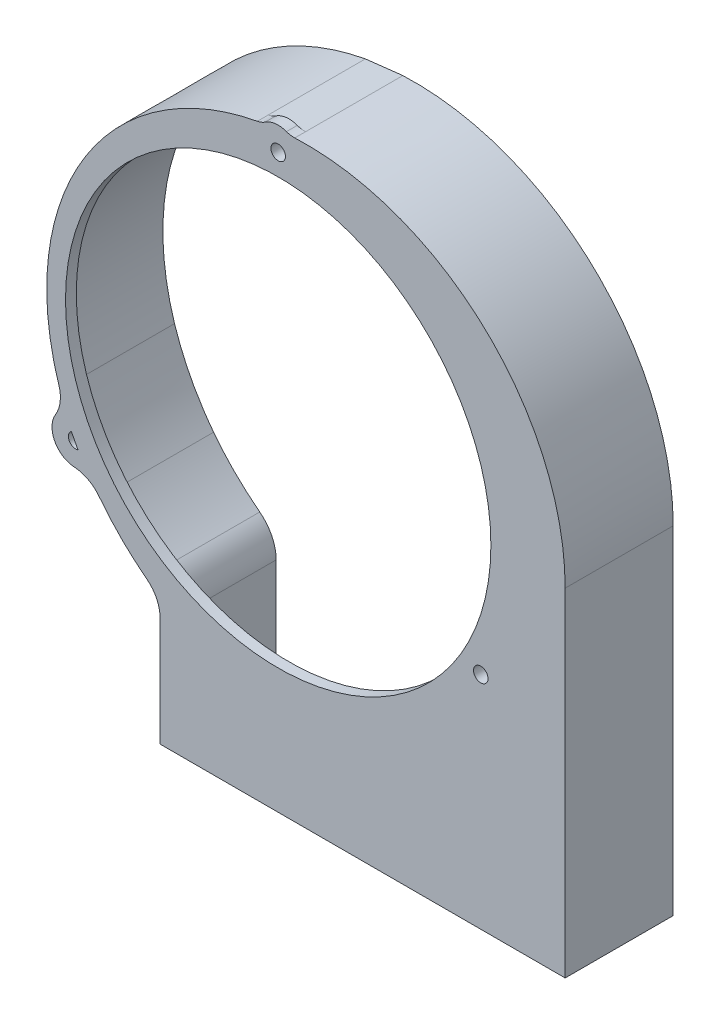
SolidWorks part; units mm, degrees
ref_plane "Front Plane" through (0, 0, 0) normal (0, 0, 1) x (1, 0, 0)
ref_plane "Top Plane" through (0, 0, 0) normal (0, 1, 0) x (1, 0, 0)
ref_plane "Right Plane" through (0, 0, 0) normal (1, 0, 0) x (0, 0, -1)
sketch "Sketch1" plane through (0, 0, 0) normal (0, 0, 1) x (1, 0, 0)
  line L0 (-2.9, 34.641) -> (2.9, 34.641) construction
  line L1 (0, 37.541) -> (0, -32.5) construction
  line L2 (-2.9, 34.641) -> (-2.9, 33.7141) construction
  line L3 (2.9, 34.641) -> (2.9, 33.7141) construction
  line L4 (28.55, -19.832) -> (27.7473, -19.3685) construction
  line L5 (31.45, -14.809) -> (30.6473, -14.3456) construction
  line L6 (-31.45, -14.809) -> (-30.6473, -14.3456) construction
  line L7 (-28.55, -19.832) -> (-27.7473, -19.3685) construction
  line L8 (0, 0) -> (2.9, 32.3704) construction
  line L9 (0, 0) -> (26.5366, -18.6636) construction
  line L10 (0, 0) -> (-29.4836, -13.6737) construction
  line L11 (0, 0) -> (-4.9858, 10.9152) construction
  line L12 (22.4164, -0.1297) -> (13.1694, 0.7526) construction
  line L13 (-11.0959, 19.478) -> (-7.2365, 11.0288) construction
  line L14 (12.7895, -3.2293) -> (22.0364, -4.1116) construction
  line L15 (-3.5981, 12.6907) -> (-7.4575, 21.1399) construction
  line L16 (-117.663, 0) -> (152.468, 0) construction
  line L17 (-11.3205, -19.3483) -> (-5.933, -11.7813) construction
  line L18 (-9.1914, -9.4614) -> (-14.579, -17.0283) construction
  line L19 (0, 0) -> (-6.9599, -9.7754) construction
  line L20 (-17.5, -50) -> (42.5, -50)
  line L21 (0, 0) -> (23.991, -2.289) construction
  line L22 (-17.5, -50) -> (-17.5, -33.7719)
  line L23 (0, -32.5) -> (-11.3205, -32.5) construction
  line L24 (42.5, -50) -> (42.5, -32.5)
  line L27 (10, -109.7237) -> (10, 118.4601) construction
  line L28 (42.5, -32.5) -> (42.5, 0) construction
  line L30 (42.5, -32.5) -> (42.5, 0)
  line L31 (-31.75, -14.2894) -> (-31.4852, -14.1365)
  line L32 (-28.25, -20.3516) -> (-28.2308, -20.3405)
  line L34 (-31.75, -14.2894) -> (-30.9473, -13.826) construction
  line L35 (-28.25, -20.3516) -> (-27.4473, -19.8881) construction
  arc A0 (-4.2059, 32.2267) -> (-30.0121, -12.471) centre (0, 0) ccw construction
  circle A1 centre (0, 34.641) radius 1.075 construction
  arc A2 (2.9, 34.641) -> (-2.9, 34.641) centre (0, 34.641) ccw construction
  arc A3 (28.55, -19.832) -> (31.45, -14.809) centre (30, -17.3205) ccw construction
  circle A4 centre (30, -17.3205) radius 1.075 construction
  arc A5 (-31.45, -14.809) -> (-28.55, -19.832) centre (-30, -17.3205) ccw construction
  circle A6 centre (-30, -17.3205) radius 1.075 construction
  arc A7 (-25.8062, -19.7558) -> (25.8062, -19.7558) centre (0, 0) ccw construction
  arc A8 (30.0121, -12.471) -> (4.2059, 32.2267) centre (0, 0) ccw construction
  arc A9 (-27.7473, -19.3685) -> (-25.8062, -19.7558) centre (-26.9973, -20.6676) cw construction
  arc A10 (-30.6473, -14.3456) -> (-30.0121, -12.471) centre (-31.3973, -13.0465) ccw construction
  arc A11 (27.7473, -19.3685) -> (25.8062, -19.7558) centre (26.9973, -20.6676) ccw construction
  arc A12 (30.6473, -14.3456) -> (30.0121, -12.471) centre (31.3973, -13.0465) cw construction
  arc A13 (2.9, 33.7141) -> (4.2059, 32.2267) centre (4.4, 33.7141) ccw construction
  arc A14 (-2.9, 33.7141) -> (-4.2059, 32.2267) centre (-4.4, 33.7141) cw construction
  arc A15 (-13.2873, 20.1062) -> (-16.8496, -17.2308) centre (0, 0) ccw construction
  arc A16 (11.8328, 1.9963) -> (-1.9855, 11.8346) centre (0, 0) ccw construction
  arc A17 (24.0561, 1.454) -> (-6.4975, 23.2076) centre (0, 0) ccw construction
  arc A18 (-10.7688, -21.5602) -> (23.3471, -5.9768) centre (0, 0) ccw construction
  arc A19 (-4.1876, -11.2456) -> (11.2418, -4.1978) centre (0, 0) ccw construction
  arc A20 (-7.6452, 9.2494) -> (-9.2563, -7.6368) centre (0, 0) ccw construction
  arc A21 (-11.3205, -19.3483) -> (-10.7688, -21.5602) centre (-10.0986, -20.2183) ccw construction
  arc A22 (-14.579, -17.0283) -> (-16.8496, -17.2308) centre (-15.8009, -16.1583) cw construction
  arc A23 (-9.1914, -9.4614) -> (-9.2563, -7.6368) centre (-10.4134, -8.5914) ccw construction
  arc A24 (-5.933, -11.7813) -> (-4.1876, -11.2456) centre (-4.711, -12.6513) cw construction
  arc A25 (12.7895, -3.2293) -> (11.2418, -4.1978) centre (12.647, -4.7226) ccw construction
  arc A26 (22.0364, -4.1116) -> (23.3471, -5.9768) centre (21.894, -5.6048) cw construction
  arc A27 (13.1694, 0.7526) -> (11.8328, 1.9963) centre (13.3119, 2.2458) cw construction
  arc A28 (-11.0959, 19.478) -> (-13.2873, 20.1062) centre (-12.4603, 18.8548) ccw construction
  arc A29 (-6.4975, 23.2076) -> (-7.4575, 21.1399) centre (-6.0931, 21.7631) ccw construction
  arc A30 (-3.5981, 12.6907) -> (-1.9855, 11.8346) centre (-2.2337, 13.3139) ccw construction
  arc A31 (-7.2365, 11.0288) -> (-7.6452, 9.2494) centre (-8.6009, 10.4055) cw construction
  arc A32 (24.0561, 1.454) -> (22.4164, -0.1297) centre (22.5588, 1.3635) cw construction
  circle A33 centre (0, 0) radius 31 construction
  arc A34 (-32.9882, -15.4983) -> (-30.1991, -20.8148) centre (-30, -17.3205) ccw
  arc A35 (1.2258, 37.9193) -> (-1.9352, 37.5573) centre (0, 34.641) ccw
  circle A36 centre (0, 0) radius 31.5
  arc A37 (3.5, 34.641) -> (-3.5, 34.641) centre (0, 34.641) ccw construction
  circle A38 centre (0, 34.641) radius 1.075
  circle A39 centre (30, -17.3205) radius 1.075
  circle A40 centre (-30, -17.3205) radius 1.075
  arc A41 (-17.5, -33.7719) -> (-19.4614, -29.8011) centre (-22.5, -33.7719) ccw
  arc A42 (-31.75, -14.2894) -> (-28.25, -20.3516) centre (-30, -17.3205) ccw construction
  arc A43 (-26.5184, -22.7609) -> (-30.1991, -20.8148) centre (-30.4836, -25.8067) ccw
  arc A44 (-32.4964, -11.3671) -> (-32.9882, -15.4983) centre (-37.2571, -12.8951) cw
  arc A45 (-1.9352, 37.5573) -> (-3.0921, 37.0875) centre (-3.6722, 40.1749) cw
  arc A46 (2.459, 37.7232) -> (1.2258, 37.9193) centre (2.326, 40.8618) cw
  ellipse E0 centre (4.1114, 0) end of major axis (-34.2773, 0) minor radius 37.7582 (42.5, 0) -> (2.459, 37.7232) ccw
  ellipse E1 centre (4.1114, 0) end of major axis (-34.2773, 0) minor radius 37.7582 (-26.5184, -22.7609) -> (-19.4614, -29.8011) ccw
  ellipse E2 centre (4.1114, 0) end of major axis (-34.2773, 0) minor radius 37.7582 (-3.0921, 37.0875) -> (-32.4964, -11.3671) ccw
  point P2 (10, -41.25)
  point P25 (32.5, 0)
  point P60 (0, 0)
  point P88 (10, 0)
  dimension "D1" = 65
  dimension "D2" = 2.15
  dimension "D3" = 5.8
  dimension "D6" = 1.5
  dimension "D7" = 8.4
  dimension "D8" = 24
  dimension "D12" = 1.5
  dimension "D13" = 1.5
  dimension "D14" = 62
  dimension "D17" = 5
  dimension "D23" = 5
  dimension "D24" = 3.1414
  dimension "D5" = 120
  dimension "D9" = 2
  dimension "D10" = 2
  dimension "D15" = 60
  dimension "D16" = 50
  dimension "D18" = 10
  dimension "D22" = 60
  dimension "D19" = 0.6
  dimension "D20" = 0.6
  dimension "D21" = 0.5
  dimension "D4" = 3
  dimension "D11" = 3
extrude "extrude-base" add sketch "Sketch1" along normal blind 1.6 contours A45 E2 A44 A34 A43 E1 A41 L22 L20 L24 L30 E0 A46 A35 A36 A38 A39 A40 region at (-16.3311, -41.8859, 0)
sketch "Sketch10" plane through (0, 0, 1.6) normal (0, 0, 1) x (1, 0, 0)
  line L6 (-17.5, -33.7719) -> (-17.5, -50)
  line L7 (-17.5, -50) -> (42.5, -50)
  line L8 (42.5, -50) -> (42.5, 0)
  line L9 (-17.5, -33.7719) -> (-17.5, -50)
  line L10 (-17.5, -50) -> (-16.3, -50)
  line L11 (42.5, -50) -> (42.5, 0)
  line L12 (-16.3, -48.8) -> (-16.3, -50)
  line L13 (41.3, -48.8) -> (41.3, -50)
  line L14 (41.3, -50) -> (42.5, -50)
  line L15 (-16.3, -33.7719) -> (-16.3, -48.8)
  line L16 (-16.3, -48.8) -> (41.3, -48.8)
  line L17 (41.3, -48.8) -> (41.3, 0)
  line L18 (-16.3, -33.7719) -> (-16.3, -48.8)
  line L19 (-2.8704, 35.9081) -> (2.5098, 36.5243)
  line L20 (41.3, -48.8) -> (41.3, 0)
  line L21 (-3.0921, 37.0875) -> (2.459, 37.7232)
  arc A14 (-3.0921, 37.0875) -> (-1.9352, 37.5573) centre (-3.6722, 40.1749) ccw
  arc A15 (-32.9882, -15.4983) -> (-32.4964, -11.3671) centre (-37.2571, -12.8951) ccw
  arc A16 (-32.9882, -15.4983) -> (-30.1991, -20.8148) centre (-30, -17.3205) ccw
  arc A17 (-26.5184, -22.7609) -> (-30.1991, -20.8148) centre (-30.4836, -25.8067) ccw
  arc A18 (-17.5, -33.7719) -> (-19.4614, -29.8011) centre (-22.5, -33.7719) ccw
  arc A19 (1.2258, 37.9193) -> (2.459, 37.7232) centre (2.326, 40.8618) ccw
  arc A20 (1.2258, 37.9193) -> (-1.9352, 37.5573) centre (0, 34.641) ccw
  arc A22 (-32.379, -11.798) -> (-32.4964, -11.3671) centre (-37.2571, -12.8951) ccw
  arc A24 (-26.5184, -22.7609) -> (-26.826, -22.3976) centre (-30.4836, -25.8067) ccw
  arc A25 (-17.5, -33.7719) -> (-19.4614, -29.8011) centre (-22.5, -33.7719) ccw
  arc A35 (-2.8704, 35.9081) -> (-1.2717, 36.5575) centre (-3.6722, 40.1749) ccw
  arc A36 (-31.9637, -16.1231) -> (-31.3538, -11.0004) centre (-37.2571, -12.8951) ccw
  arc A37 (-31.9637, -16.1231) -> (-30.1309, -19.6168) centre (-30, -17.3205) ccw
  arc A38 (-25.5667, -22.03) -> (-30.1309, -19.6168) centre (-30.4836, -25.8067) ccw
  arc A39 (-16.3, -33.7719) -> (-18.7322, -28.8481) centre (-22.5, -33.7719) ccw
  arc A40 (0.8055, 36.7953) -> (2.5098, 36.5243) centre (2.326, 40.8618) ccw
  arc A41 (0.8055, 36.7953) -> (-1.2717, 36.5575) centre (0, 34.641) ccw
  arc A46 (-16.3, -33.7719) -> (-18.7322, -28.8481) centre (-22.5, -33.7719) ccw
  ellipse E6 centre (4.1114, 0) end of major axis (-34.2773, 0) minor radius 37.7582 (-3.0921, 37.0875) -> (-32.4964, -11.3671) ccw
  ellipse E7 centre (4.1114, 0) end of major axis (-34.2773, 0) minor radius 37.7582 (-26.5184, -22.7609) -> (-19.4614, -29.8011) ccw
  ellipse E8 centre (4.1114, 0) end of major axis (-34.2773, 0) minor radius 37.7582 (42.5, 0) -> (2.459, 37.7232) ccw
  ellipse E9 centre (4.1114, 0) end of major axis (-34.2773, 0) minor radius 37.7582 (-3.0921, 37.0875) -> (-32.4964, -11.3671) ccw
  ellipse E10 centre (4.1114, 0) end of major axis (-34.2773, 0) minor radius 37.7582 (-26.5184, -22.7609) -> (-19.4614, -29.8011) ccw
  ellipse E11 centre (4.1114, 0) end of major axis (-34.2773, 0) minor radius 37.7582 (42.5, 0) -> (2.459, 37.7232) ccw
  spline S0 degree 3 poles (2530.5832, -5387.9475) (692.9967, -896.5243) (145.8987, 98.1948) (-11.4801, 33.2143) (-12.6478, 32.6607) (-14.3638, 31.7341) (-14.9312, 31.4083) (-16.0415, 30.7315) (-16.5857, 30.3799) (-19.2528, 28.5568) (-21.2158, 26.8924) (-23.8996, 24.0813) (-24.7539, 23.086) (-26.3349, 21.032) (-27.7971, 18.9073) (-29.0256, 16.6438) (-29.8578, 14.8931) (-30.1203, 14.3007) (-30.6148, 13.0978) (-30.8473, 12.486) (-31.9191, 9.4172) (-32.5015, 6.9082) (-32.8915, 3.7057) (-32.9525, 3.0618) (-33.0396, 1.7673) (-33.0659, 1.115) (-33.0911, -0.8408) (-33.037, -2.1344) (-17.0784, -169.1919) (1132.0811, -170.6193) (5943.9195, 359.0893) knots -8.074292 -8.074292 -8.074292 -8.074292 0.125 0.125 0.1875 0.1875 0.21875 0.21875 0.25 0.25 0.375 0.375 0.4375 0.4375 0.5 0.5625 0.5625 0.59375 0.59375 0.625 0.625 0.75 0.75 0.78125 0.78125 0.8125 0.8125 0.875 0.875 8.946378 8.946378 8.946378 8.946378 only from (-2.8704, 35.9081) to (-31.3538, -11.0004)
  spline S1 degree 3 poles (3866.3832, 4527.9049) (440.261, 875.0538) (-131.6317, 83.3001) (98.4859, -146.1976) (1052.9272, 568.8562) (4552.9565, 3835.6232) knots -47.451296 -47.451296 -47.451296 -47.451296 0.5 0.5 53.54289 53.54289 53.54289 53.54289 only from (-25.5667, -22.03) to (-18.7322, -28.8481)
  spline S2 degree 3 poles (-5764.2897, -1464.7865) (-908.0196, -474.8461) (72.9243, -147.1511) (40.2816, 8.5858) (39.966, 9.7833) (39.3964, 11.5631) (39.19, 12.1551) (38.749, 13.3213) (38.5142, 13.8965) (37.2709, 16.7338) (36.055, 18.8812) (33.9007, 21.9191) (33.1227, 22.9055) (31.4857, 24.7761) (30.6249, 25.6643) (28.8208, 27.3489) (27.8776, 28.1452) (26.4006, 29.2706) (25.8979, 29.6341) (24.8714, 30.3378) (24.3462, 30.6789) (21.6878, 32.3115) (19.4634, 33.3865) (15.986, 34.6657) (14.8032, 35.0362) (12.9926, 35.5057) (12.3825, 35.6478) (11.1621, 35.9003) (10.5505, 36.0112) (-168.8774, 63.9896) (-470.9936, -1191.6349) (-1099.6628, -5846.5117) knots -7.869177 -7.869177 -7.869177 -7.869177 0.125 0.125 0.1875 0.1875 0.21875 0.21875 0.25 0.25 0.375 0.375 0.4375 0.4375 0.5 0.5 0.5625 0.5625 0.59375 0.59375 0.625 0.625 0.75 0.75 0.8125 0.8125 0.84375 0.84375 0.875 0.875 9.988994 9.988994 9.988994 9.988994 only from (41.3, 0) to (2.5098, 36.5243)
  spline S3 degree 3 poles (-2.8704, 35.9081) (-5.4365, 35.426) (-7.9084, 34.689) (-11.4801, 33.2143) (-12.6478, 32.6607) (-14.3638, 31.7341) (-14.9312, 31.4083) (-16.0415, 30.7315) (-16.5857, 30.3799) (-19.2528, 28.5568) (-21.2158, 26.8924) (-23.8996, 24.0813) (-24.7539, 23.086) (-26.3349, 21.032) (-27.7971, 18.9073) (-29.0256, 16.6438) (-29.8578, 14.8931) (-30.1203, 14.3007) (-30.6148, 13.0978) (-30.8473, 12.486) (-31.9191, 9.4172) (-32.5015, 6.9082) (-32.8915, 3.7057) (-32.9525, 3.0618) (-33.0396, 1.7673) (-33.0659, 1.115) (-33.0911, -0.8408) (-33.037, -2.1344) (-32.6691, -5.9853) (-32.1521, -8.5132) (-31.3538, -11.0004) knots 0 0 0 0 0.125 0.125 0.1875 0.1875 0.21875 0.21875 0.25 0.25 0.375 0.375 0.4375 0.4375 0.5 0.5625 0.5625 0.59375 0.59375 0.625 0.625 0.75 0.75 0.78125 0.78125 0.8125 0.8125 0.875 0.875 1 1 1 1
  spline S4 degree 3 poles (-25.5667, -22.03) (-24.5781, -23.3171) (-23.5128, -24.5275) (-21.2343, -26.7999) (-20.021, -27.8619) (-18.7322, -28.8481) knots 0 0 0 0 0.5 0.5 1 1 1 1
  spline S5 degree 3 poles (41.3, 0) (41.3, 2.5028) (41.0413, 4.9614) (40.2816, 8.5858) (39.966, 9.7833) (39.3964, 11.5631) (39.19, 12.1551) (38.749, 13.3213) (38.5142, 13.8965) (37.2709, 16.7338) (36.055, 18.8812) (33.9007, 21.9191) (33.1227, 22.9055) (31.4857, 24.7761) (30.6249, 25.6643) (28.8208, 27.3489) (27.8776, 28.1452) (26.4006, 29.2706) (25.8979, 29.6341) (24.8714, 30.3378) (24.3462, 30.6789) (21.6878, 32.3115) (19.4634, 33.3865) (15.986, 34.6657) (14.8032, 35.0362) (12.9926, 35.5057) (12.3825, 35.6478) (11.1621, 35.9003) (10.5505, 36.0112) (7.4849, 36.4892) (5.0092, 36.6302) (2.5098, 36.5243) knots 0 0 0 0 0.125 0.125 0.1875 0.1875 0.21875 0.21875 0.25 0.25 0.375 0.375 0.4375 0.4375 0.5 0.5 0.5625 0.5625 0.59375 0.59375 0.625 0.625 0.75 0.75 0.8125 0.8125 0.84375 0.84375 0.875 0.875 1 1 1 1
  spline S6 degree 2 poles (-31.3538, -11.0004) (-29.4029, -17.01) (-25.5667, -22.03) knots 0 0 0 1 1 1
  spline S7 degree 2 poles (-32.4964, -11.3671) (-30.7973, -17.7895) (-26.5184, -22.7609) knots 0 0 0 1 1 1
  circle M30 centre (-30, -17.3205) radius 1.075
  ellipse M32 centre (4.1114, 0) end of major axis (-34.2773, 0) minor radius 37.7582 (-3.0921, 37.0875) -> (-32.4964, -11.3671) ccw
  arc M33 (-32.4964, -11.3671) -> (-32.9882, -15.4983) centre (-37.2571, -12.8951) cw
  arc M35 (-30.1991, -20.8148) -> (-26.5184, -22.7609) centre (-30.4836, -25.8067) cw
  ellipse M36 centre (4.1114, 0) end of major axis (-34.2773, 0) minor radius 37.7582 (-26.5184, -22.7609) -> (-19.4614, -29.8011) ccw
  arc M37 (-19.4614, -29.8011) -> (-17.5, -33.7719) centre (-22.5, -33.7719) cw
  line M38 (-17.5, -33.7719) -> (-17.5, -50)
  line M39 (-17.5, -50) -> (42.5, -50)
  line M40 (42.5, -50) -> (42.5, 0)
  ellipse M41 centre (4.1114, 0) end of major axis (-34.2773, 0) minor radius 37.7582 (42.5, 0) -> (2.459, 37.7232) ccw
  dimension "D1" = 0
  dimension "D2" = 1.2
extrude "Boss-Extrude9" add sketch "Sketch10" against normal blind 16 contours S7 L12 L18 A46 S4 S6 S3 L19 S5 L20 L13 L21 M33 M30 M35 M36 M37 M38 M39 M40 M41 M32 | S7 M30 region at (-17.7249, -31.4131, 1.6) region at (-29.0968, -19.0494, 1.6) region at (42.2549, -49.4, 1.6) region at (-20.3138, -27.9158, 1.6) region at (-29.1853, -16.2873, 1.6) region at (-29.6794, -17.1526, 1.6) region at (-31.8554, -11.424, 1.6) region at (1.1387, 36.4443, 1.6) region at (-0.1851, 36.2552, 1.6) region at (-1.4168, 36.1541, 1.6) region at (12.262, 36.3747, 1.6) region at (-0.2178, 36.5362, 1.6)
sketch "Sketch11" plane through (-4.2323, 36.9569, 0) normal (-0.1138, 0.9935, 0) x (0.9935, 0.1138, 0)
  line L0 (1.1477, 14.4) -> (1.1477, 0) construction
  line L1 (6.735, 14.4) -> (1.1477, 14.4)
  line L2 (6.735, 14.4) -> (6.735, 8.4)
  line L3 (6.735, 8.4) -> (1.1477, 8.4)
  line L4 (1.1477, 14.4) -> (1.1477, 8.4)
  dimension "D1" = 6
sketch "Sketch12" plane through (0, 0, -14.4) normal (0, 0, -1) x (-1, 0, 0)
  line L8 (3.0921, 37.0875) -> (-2.459, 37.7232)
  line L9 (-42.5, 0) -> (-42.5, -50)
  line L10 (-42.5, -50) -> (-41.3, -50)
  line L11 (-41.3, -50) -> (-41.3, 0)
  line L12 (-2.5098, 36.5243) -> (2.8704, 35.9081)
  line L13 (16.3, -33.7719) -> (16.3, -50)
  line L14 (16.3, -50) -> (17.5, -50)
  line L15 (17.5, -50) -> (17.5, -33.7719)
  line L16 (3.0921, 37.0875) -> (-2.459, 37.7232)
  line L17 (-42.5, 0) -> (-42.5, -50)
  line L18 (-42.5, -50) -> (-41.3, -50)
  line L19 (-41.3, -50) -> (-41.3, 0)
  line L20 (-2.5098, 36.5243) -> (2.8704, 35.9081)
  line L21 (16.3, -33.7719) -> (16.3, -50)
  line L22 (16.3, -50) -> (17.5, -50)
  line L23 (17.5, -50) -> (17.5, -33.7719)
  arc A4 (32.4964, -11.3671) -> (32.379, -11.798) centre (37.2571, -12.8951) ccw
  arc A5 (18.7322, -28.8481) -> (16.3, -33.7719) centre (22.5, -33.7719) ccw
  arc A6 (19.4614, -29.8011) -> (17.5, -33.7719) centre (22.5, -33.7719) ccw
  arc A7 (26.826, -22.3976) -> (26.5184, -22.7609) centre (30.4836, -25.8067) ccw
  arc A8 (32.4964, -11.3671) -> (32.379, -11.798) centre (37.2571, -12.8951) ccw
  arc A9 (18.7322, -28.8481) -> (16.3, -33.7719) centre (22.5, -33.7719) ccw
  arc A10 (19.4614, -29.8011) -> (17.5, -33.7719) centre (22.5, -33.7719) ccw
  arc A11 (26.826, -22.3976) -> (26.5184, -22.7609) centre (30.4836, -25.8067) ccw
  ellipse E3 centre (-4.1114, 0) end of major axis (34.2773, 0) minor radius 37.7582 (32.4964, -11.3671) -> (3.0921, 37.0875) ccw
  ellipse E4 centre (-4.1114, 0) end of major axis (34.2773, 0) minor radius 37.7582 (-2.459, 37.7232) -> (-42.5, 0) ccw
  ellipse E5 centre (-4.1114, 0) end of major axis (34.2773, 0) minor radius 37.7582 (19.4614, -29.8011) -> (26.5184, -22.7609) ccw
  ellipse E6 centre (-4.1114, 0) end of major axis (34.2773, 0) minor radius 37.7582 (32.4964, -11.3671) -> (3.0921, 37.0875) ccw
  ellipse E7 centre (-4.1114, 0) end of major axis (34.2773, 0) minor radius 37.7582 (-2.459, 37.7232) -> (-42.5, 0) ccw
  ellipse E8 centre (-4.1114, 0) end of major axis (34.2773, 0) minor radius 37.7582 (19.4614, -29.8011) -> (26.5184, -22.7609) ccw
  parabola Q2 (31.3538, -11.0004) -> (25.5667, -22.03) focus (12.8004, -8.3028) apex (28.9283, -16.7689)
  parabola Q3 (26.826, -22.3976) -> (32.379, -11.798) focus (17.5859, -11.2941) apex (29.763, -18.1432)
  parabola Q4 (31.3538, -11.0004) -> (25.5667, -22.03) focus (12.8004, -8.3028) apex (28.9283, -16.7689)
  parabola Q5 (26.826, -22.3976) -> (32.379, -11.798) focus (17.5859, -11.2941) apex (29.763, -18.1432)
  spline S3 degree 3 poles (3806.477, -1057.1498) (632.9436, -379.1252) (-67.9956, -123.6365) (-40.2816, 8.5858) (-39.966, 9.7833) (-39.3964, 11.5631) (-39.19, 12.1551) (-38.749, 13.3213) (-38.5142, 13.8965) (-37.2709, 16.7338) (-36.055, 18.8812) (-33.9007, 21.9191) (-33.1227, 22.9055) (-31.4857, 24.7761) (-30.6249, 25.6643) (-28.8208, 27.3489) (-27.8776, 28.1452) (-26.4006, 29.2706) (-25.8979, 29.6341) (-24.8714, 30.3378) (-24.3462, 30.6789) (-21.6878, 32.3115) (-19.4634, 33.3865) (-15.986, 34.6657) (-14.8032, 35.0362) (-12.9926, 35.5057) (-12.3825, 35.6478) (-11.1621, 35.9003) (-10.5505, 36.0112) (140.2915, 59.5322) (377.5503, -822.9805) (822.3658, -3866.0551) knots -6.652703 -6.652703 -6.652703 -6.652703 0.125 0.125 0.1875 0.1875 0.21875 0.21875 0.25 0.25 0.375 0.375 0.4375 0.4375 0.5 0.5 0.5625 0.5625 0.59375 0.59375 0.625 0.625 0.75 0.75 0.8125 0.8125 0.84375 0.84375 0.875 0.875 8.532003 8.532003 8.532003 8.532003 only from (-41.3, 0) to (-2.5098, 36.5243)
  spline S4 degree 3 poles (-1764.9411, -3540.4206) (-532.6042, -613.2952) (-121.66, 88.1869) (11.4801, 33.2143) (12.6478, 32.6607) (14.3638, 31.7341) (14.9312, 31.4083) (16.0415, 30.7315) (16.5857, 30.3799) (19.2528, 28.5568) (21.2158, 26.8924) (23.8996, 24.0813) (24.7539, 23.086) (26.3349, 21.032) (27.7971, 18.9073) (29.0256, 16.6438) (29.8578, 14.8931) (30.1203, 14.3007) (30.6148, 13.0978) (30.8473, 12.486) (31.9191, 9.4172) (32.5015, 6.9082) (32.8915, 3.7057) (32.9525, 3.0618) (33.0396, 1.7673) (33.0659, 1.115) (33.0911, -0.8408) (33.037, -2.1344) (19.5411, -143.4116) (-802.0671, -166.2006) (-3955.2106, 149.1132) knots -6.801853 -6.801853 -6.801853 -6.801853 0.125 0.125 0.1875 0.1875 0.21875 0.21875 0.25 0.25 0.375 0.375 0.4375 0.4375 0.5 0.5625 0.5625 0.59375 0.59375 0.625 0.625 0.75 0.75 0.78125 0.78125 0.8125 0.8125 0.875 0.875 7.691157 7.691157 7.691157 7.691157 only from (2.8704, 35.9081) to (31.3538, -11.0004)
  spline S5 degree 3 poles (-2504.296, 3063.7496) (-283.3423, 651.8971) (115.1643, 66.877) (-79.4901, -127.253) (-773.4953, 364.7242) (-3084.636, 2477.728) knots -40.22404 -40.22404 -40.22404 -40.22404 0.5 0.5 45.206001 45.206001 45.206001 45.206001 only from (25.5667, -22.03) to (18.7322, -28.8481)
  spline S6 degree 3 poles (-41.3, 0) (-41.3, 2.5028) (-41.0413, 4.9614) (-40.2816, 8.5858) (-39.966, 9.7833) (-39.3964, 11.5631) (-39.19, 12.1551) (-38.749, 13.3213) (-38.5142, 13.8965) (-37.2709, 16.7338) (-36.055, 18.8812) (-33.9007, 21.9191) (-33.1227, 22.9055) (-31.4857, 24.7761) (-30.6249, 25.6643) (-28.8208, 27.3489) (-27.8776, 28.1452) (-26.4006, 29.2706) (-25.8979, 29.6341) (-24.8714, 30.3378) (-24.3462, 30.6789) (-21.6878, 32.3115) (-19.4634, 33.3865) (-15.986, 34.6657) (-14.8032, 35.0362) (-12.9926, 35.5057) (-12.3825, 35.6478) (-11.1621, 35.9003) (-10.5505, 36.0112) (-7.4849, 36.4892) (-5.0092, 36.6302) (-2.5098, 36.5243) knots 0 0 0 0 0.125 0.125 0.1875 0.1875 0.21875 0.21875 0.25 0.25 0.375 0.375 0.4375 0.4375 0.5 0.5 0.5625 0.5625 0.59375 0.59375 0.625 0.625 0.75 0.75 0.8125 0.8125 0.84375 0.84375 0.875 0.875 1 1 1 1
  spline S7 degree 3 poles (2.8704, 35.9081) (5.4365, 35.426) (7.9084, 34.689) (11.4801, 33.2143) (12.6478, 32.6607) (14.3638, 31.7341) (14.9312, 31.4083) (16.0415, 30.7315) (16.5857, 30.3799) (19.2528, 28.5568) (21.2158, 26.8924) (23.8996, 24.0813) (24.7539, 23.086) (26.3349, 21.032) (27.7971, 18.9073) (29.0256, 16.6438) (29.8578, 14.8931) (30.1203, 14.3007) (30.6148, 13.0978) (30.8473, 12.486) (31.9191, 9.4172) (32.5015, 6.9082) (32.8915, 3.7057) (32.9525, 3.0618) (33.0396, 1.7673) (33.0659, 1.115) (33.0911, -0.8408) (33.037, -2.1344) (32.6691, -5.9853) (32.1521, -8.5132) (31.3538, -11.0004) knots 0 0 0 0 0.125 0.125 0.1875 0.1875 0.21875 0.21875 0.25 0.25 0.375 0.375 0.4375 0.4375 0.5 0.5625 0.5625 0.59375 0.59375 0.625 0.625 0.75 0.75 0.78125 0.78125 0.8125 0.8125 0.875 0.875 1 1 1 1
  spline S8 degree 3 poles (25.5667, -22.03) (24.5781, -23.3171) (23.5128, -24.5275) (21.2343, -26.7999) (20.021, -27.8619) (18.7322, -28.8481) knots 0 0 0 0 0.5 0.5 1 1 1 1
  dimension "D1" = 0
